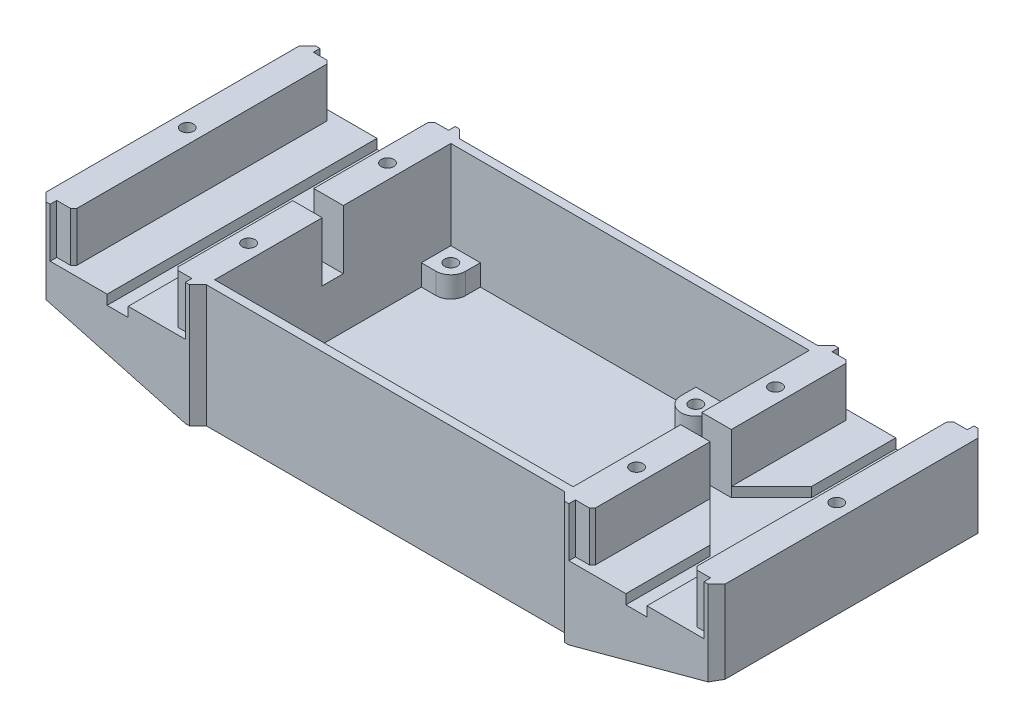
SolidWorks part; units mm, degrees
material "Nylon 101"
ref_plane "Front Plane" through (0, 0, 0) normal (0, 0, 1) x (1, 0, 0)
ref_plane "Top Plane" through (0, 0, 0) normal (0, 1, 0) x (1, 0, 0)
ref_plane "Right Plane" through (0, 0, 0) normal (1, 0, 0) x (0, 0, -1)
sketch "Sketch1" plane through (0, 0, 0) normal (0, 1, 0) x (1, 0, 0)
  line L0 (-42.5, 0) -> (42.5, 0) construction
  line L1 (-42.5, -28) -> (42.5, -28)
  line L2 (-42.5, -28) -> (-42.5, 28)
  line L3 (-42.5, 28) -> (42.5, 28)
  line L4 (42.5, -28) -> (42.5, 28)
  line L5 (-42.5, -28) -> (42.5, 28) construction
  line L6 (-42.5, 28) -> (42.5, -28) construction
  line L11 (-39, 0) -> (-39, -24.5) construction
  line L12 (-39, 0) -> (-39, 24.5) construction
  line L13 (19.09, 0) -> (19.09, 24.5) construction
  line L14 (19.09, 0) -> (19.09, -24.5) construction
  line L16 (-44.5, -30) -> (44.5, -30)
  line L17 (-44.5, -30) -> (-44.5, 30)
  line L18 (-44.5, 30) -> (44.5, 30)
  line L19 (44.5, -30) -> (44.5, 30)
  circle A0 centre (-39, 24.5) radius 1.5
  circle A1 centre (19.09, 24.5) radius 1.5
  circle A2 centre (-39, -24.5) radius 1.5
  circle A3 centre (19.09, -24.5) radius 1.5
  circle A4 centre (-39, 24.5) radius 3.5
  circle A5 centre (19.09, 24.5) radius 3.5
  circle A6 centre (-39, -24.5) radius 3.5
  circle A7 centre (19.09, -24.5) radius 3.5
  point P0 (0, 0)
  point P6 (0, 0)
  dimension "D9" = 3
  dimension "D10" = 3
  dimension "D11" = 3
  dimension "D12" = 3
  dimension "D13" = 7
  dimension "D14" = 7
  dimension "D15" = 7
  dimension "D16" = 7
  dimension "D1" = 85
  dimension "D2" = 56
  dimension "D3" = 39
  dimension "D4" = 24.5
  dimension "D5" = 24.5
  dimension "D6" = 19.09
  dimension "D7" = 24.5
  dimension "D8" = 24.5
  dimension "D17" = 2
  dimension "D18" = 2
  dimension "D19" = 2
  dimension "D20" = 2
sketch "Sketch2" plane through (0, 0, 0) normal (0, 1, 0) x (1, 0, 0)
  line L1 (-42.5, -28) -> (42.5, -28)
  line L2 (-42.5, -28) -> (-42.5, 28)
  line L3 (-42.5, 28) -> (42.5, 28)
  line L4 (42.5, -28) -> (42.5, 28)
extrude "Boss-Extrude4" add sketch "Sketch2" along normal blind 3
sketch "Sketch3" plane through (0, 0, 0) normal (0, 1, 0) x (1, 0, 0)
  line L0 (0, 0) -> (-44.5, 0) construction
  line L1 (-44.5, -30) -> (44.5, -30)
  line L2 (-44.5, -30) -> (-44.5, 30)
  line L3 (-44.5, 30) -> (44.5, 30)
  line L4 (44.5, -30) -> (44.5, 30)
  line L5 (-42.5, 28) -> (42.5, 28)
  line L6 (-42.5, 28) -> (-42.5, -28)
  line L7 (-42.5, -28) -> (42.5, -28)
  line L8 (42.5, 28) -> (42.5, -28)
  line L9 (-44.5, 0) -> (-78.5, 0) construction
  line L10 (-44.5, 30) -> (-44.5, 32)
  line L11 (-44.5, 32) -> (-78.5, 32)
  line L12 (-78.5, 32) -> (-78.5, 0)
  line L13 (-78.5, 0) -> (-78.5, -32)
  line L14 (-78.5, -32) -> (-44.5, -32)
  line L15 (-44.5, -32) -> (-44.5, -30)
  line L16 (0, 0) -> (44.5, 0) construction
  line L17 (44.5, 0) -> (78.5, 0) construction
  line L18 (44.5, 30) -> (44.5, 32)
  line L19 (44.5, 32) -> (78.5, 32)
  line L20 (78.5, 32) -> (78.5, 0)
  line L21 (78.5, 0) -> (78.5, -32)
  line L22 (78.5, -32) -> (44.5, -32)
  line L23 (44.5, -32) -> (44.5, -30)
  dimension "D1" = 44.5
  dimension "D2" = 34
  dimension "D3" = 2
  dimension "D4" = 2
  dimension "D5" = 34
  dimension "D6" = 2
  dimension "D7" = 2
extrude "Boss-Extrude5" add sketch "Sketch3" along normal blind 29 contours L1 L4 L3 L2 L5 L8 L7 L6 | L14 L15 L2 L10 L11 L12 L13 | L23 L22 L21 L20 L19 L18 L4 region at (-43.4266, 0, 0) region at (-61.5, 0, 0) region at (61.5, 0, 0)
sketch "Sketch5" plane through (0, 0, 0) normal (0, 1, 0) x (1, 0, 0)
  line L0 (15.59, 24.5) -> (15.59, 28)
  line L1 (-42.5, -28) -> (42.5, -28)
  line L2 (-42.5, -28) -> (-42.5, 28)
  line L3 (-42.5, 28) -> (42.5, 28)
  line L4 (42.5, -28) -> (42.5, 28)
  line L5 (22.59, 24.5) -> (22.59, 28)
  line L6 (15.59, -24.5) -> (15.59, -28)
  line L7 (22.59, -24.5) -> (22.59, -28)
  line L8 (-39, -21) -> (-42.5, -21)
  line L9 (-35.5, -24.5) -> (-35.5, -28)
  line L10 (-39, 21) -> (-42.5, 21)
  line L11 (-35.5, 24.5) -> (-35.5, 28)
  circle A0 centre (19.09, 24.5) radius 3.5
  circle A1 centre (19.09, -24.5) radius 3.5
  circle A2 centre (-39, 24.5) radius 3.5
  circle A3 centre (-39, -24.5) radius 3.5
extrude "Boss-Extrude10" add sketch "Sketch5" along normal blind 8 contours A2 | A2 L3 L2 | A2 L2 L10 | A2 L11 L3 | A3 L1 L9 | A3 | A3 L2 L1 | A3 L8 L2 | A1 L1 L7 | A1 | A1 L6 L1 | A0 L5 L3 | A0 L3 L0 | A0 region at (19.09, 0, -24.5) region at (16.3718, 0, -27.2182) region at (21.8082, 0, -27.2182) region at (-36.2818, 0, -27.2182) region at (-41.7182, 0, -27.2182) region at (-39, 0, -24.5) region at (-41.7182, 0, -21.7818) region at (21.8082, 0, 27.2182) region at (-41.7182, 0, 21.7818) region at (16.3718, 0, 27.2182) region at (19.09, 0, 24.5) region at (-41.7182, 0, 27.2182) region at (-39, 0, 24.5) region at (-36.2818, 0, 27.2182)
sketch "Sketch6" plane through (0, 29, 0) normal (0, 1, 0) x (1, 0, 0)
  line L0 (-44.5, 30) -> (-44.5, -30) construction
  line L1 (-44.5, -32) -> (-45.475, -32)
  line L2 (-78.5, -32) -> (-44.5, -32) construction
  line L3 (44.5, 30) -> (44.5, -30) construction
  line L4 (-45.475, -32) -> (-77.525, -32)
  line L5 (-77.525, -32) -> (-78.5, -32)
  line L6 (-44.5, 32) -> (-45.48, 32)
  line L7 (-44.5, 32) -> (-78.5, 32) construction
  line L8 (-45.48, 32) -> (-77.53, 32)
  line L9 (-77.53, 32) -> (-78.5, 32)
  line L10 (-61.5, -32) -> (-61.505, 32) construction
  line L11 (-77.525, -32) -> (-77.525, -30.43)
  line L12 (-77.525, -30.43) -> (-45.475, -30.43)
  line L13 (-45.475, -30.43) -> (-45.475, -32)
  line L14 (-77.53, 32) -> (-77.53, 30.43)
  line L15 (-77.53, 30.43) -> (-45.48, 30.43)
  line L16 (-45.48, 30.43) -> (-45.48, 32)
  line L17 (-61.5025, 0) -> (-73.5025, 0) construction
  line L18 (-61.5025, 0) -> (-49.5025, 0) construction
  line L19 (-73.5025, 0) -> (-73.5025, -30.43)
  line L20 (-73.5025, 0) -> (-73.5025, 30.43)
  line L21 (-49.5025, 0) -> (-49.5025, 30.43)
  line L22 (-49.5025, 0) -> (-49.5025, -30.43)
  line M21 (-44.5, 32) -> (-78.5, 32)
  line M23 (-78.5, -32) -> (-44.5, -32)
  dimension "D1" = 34
  dimension "D2" = 32.05
  dimension "D3" = 0.975
  dimension "D4" = 0.975
  dimension "D5" = 0.98
  dimension "D6" = 32.05
  dimension "D7" = 0.97
  dimension "D8" = 1.57
  dimension "D9" = 1.57
  dimension "D10" = 1.57
  dimension "D11" = 1.57
  dimension "D12" = 12
  dimension "D13" = 12
extrude "Cut-Extrude1" cut sketch "Sketch6" against normal blind 11.7 contours L15 L16 L14 M21 | L22 L21 L15 L20 L19 L12 | L13 L12 L11 M23 region at (-61.5, 29, 31.215) region at (-61.5025, 29, 0) region at (-61.505, 29, -31.215)
chamfer "Chamfer1" distance 2 angle 45 4 edges at (-44.5, 14.5, -30) (44.5, 14.5, -30) (44.5, 14.5, 30) (-44.5, 14.5, 30)
sketch "Sketch7" plane through (0, 29, 0) normal (0, 1, 0) x (1, 0, 0)
  line L0 (61.5, 32) -> (61.5, -32) construction
  line L1 (44.5, 32) -> (78.5, 32) construction
  line L2 (78.5, -32) -> (44.5, -32) construction
  line L3 (61.5, 32) -> (45.475, 32)
  line L4 (61.5, 32) -> (77.53, 32)
  line L5 (77.53, 32) -> (77.53, 30.43)
  line L6 (77.53, 30.43) -> (73.5, 30.43)
  line L7 (73.5, 30.43) -> (73.5, -30.43)
  line L8 (73.5, -30.43) -> (77.53, -30.43)
  line L9 (77.53, -30.43) -> (77.53, -32)
  line L10 (77.53, -32) -> (61.5, -32)
  line L11 (61.5, -32) -> (45.47, -32)
  line L12 (45.47, -32) -> (45.47, -30.43)
  line L13 (45.47, -30.43) -> (49.5, -30.43)
  line L14 (49.5, -30.43) -> (49.5, 30.43)
  line L15 (49.5, 30.43) -> (45.475, 30.43)
  line L16 (45.475, 30.43) -> (45.475, 32)
  dimension "D1" = 16.025
  dimension "D2" = 16.03
  dimension "D3" = 1.57
  dimension "D4" = 1.57
  dimension "D5" = 12
  dimension "D6" = 12
  dimension "D7" = 1.57
  dimension "D8" = 16.03
  dimension "D9" = 16.03
  dimension "D10" = 1.57
extrude "Cut-Extrude2" cut sketch "Sketch7" against normal blind 11.7
sketch "Sketch8" plane through (-78.5, 0, 0) normal (-1, 0, 0) x (0, 0, 1)
  line L1 (-32, 29) -> (32, 29)
  line L2 (-32, 29) -> (-32, 0)
  line L3 (-32, 0) -> (32, 0)
  line L4 (32, 29) -> (32, 0)
extrude "Boss-Extrude11" add sketch "Sketch8" along normal blind 2
sketch "Sketch9" plane through (78.5, 0, 0) normal (1, 0, 0) x (0, 0, -1)
  line L1 (-32, 29) -> (32, 29)
  line L2 (-32, 29) -> (-32, 0)
  line L3 (-32, 0) -> (32, 0)
  line L4 (32, 29) -> (32, 0)
extrude "Boss-Extrude12" add sketch "Sketch9" along normal blind 2
chamfer "Chamfer2" distance 2 angle 45 4 edges at (-80.5, 14.5, -32) (80.5, 14.5, -32) (80.5, 14.5, 32) (-80.5, 14.5, 32)
chamfer "Chamfer3" distance 0.75 angle 45 8 edges at (-73.5025, 23.15, -30.43) (-49.5025, 23.15, -30.43) (-73.5025, 23.15, 30.43) (-49.5025, 23.15, 30.43) (73.5, 23.15, 30.43) (49.5, 23.15, 30.43) (49.5, 23.15, -30.43) (73.5, 23.15, -30.43)
sketch "Sketch10" plane through (0, 29, 0) normal (0, 1, 0) x (1, 0, 0)
  line L0 (-61.505, 32) -> (-61.5, -32) construction
  line L1 (-45.48, 32) -> (-77.53, 32) construction
  line L2 (-77.525, -32) -> (-45.475, -32) construction
  line L3 (61.5025, 32) -> (61.5, -32) construction
  line L4 (77.53, 32) -> (45.475, 32) construction
  line L5 (45.47, -32) -> (77.53, -32) construction
  line L6 (-61.505, 32) -> (-64.005, 32)
  line L7 (-64.005, 32) -> (-64.005, -32)
  line L8 (-64.005, -32) -> (-61.5, -32)
  line L9 (-61.5, -32) -> (-59.005, -32)
  line L10 (-59.005, -32) -> (-59.005, 32)
  line L11 (-59.005, 32) -> (-61.505, 32)
  line L12 (61.5025, 32) -> (59.0025, 32)
  line L13 (59.0025, 32) -> (59.0025, -32)
  line L14 (59.0025, -32) -> (61.5, -32)
  line L15 (61.5, -32) -> (64.0025, -32)
  line L16 (64.0025, -32) -> (64.0025, 32)
  line L17 (64.0025, 32) -> (61.5025, 32)
  line L18 (-59.005, 0) -> (59.0025, 0) construction
  line L19 (-59.005, 0) -> (-59.005, 2.5)
  line L20 (-59.005, 2.5) -> (59.0025, 2.5)
  line L21 (59.0025, 2.5) -> (59.0025, 0)
  line L22 (59.0025, 0) -> (59.0025, -2.5)
  line L23 (59.0025, -2.5) -> (-59.005, -2.5)
  line L24 (-59.005, -2.5) -> (-59.005, 0)
  line M3 (-49.5025, 29.68) -> (-49.5025, -29.68)
  line M15 (49.5, -29.68) -> (49.5, 29.68)
  line M26 (42.5, 28) -> (42.5, -28)
  line M28 (-42.5, -28) -> (-42.5, 28)
  dimension "D1" = 2.5
  dimension "D2" = 2.5
  dimension "D3" = 2.5
  dimension "D4" = 2.5
  dimension "D5" = 2.5
  dimension "D6" = 2.5
sketch "Sketch11" plane through (0, 0, 32) normal (0, 0, 1) x (1, 0, 0)
  line L0 (-77.525, 17.3) -> (-77.525, 0) construction
  line L1 (-78.5, 0) -> (-44.5, 0) construction
  line L2 (-45.475, 17.3) -> (-45.475, 0) construction
  line L3 (-77.525, 8.65) -> (-45.475, 0)
  line L4 (-45.475, 0) -> (-93.8507, 13.0561)
  line L5 (45.47, 17.3) -> (45.47, 0) construction
  line L6 (78.5, 0) -> (44.5, 0) construction
  line L7 (77.53, 17.3) -> (77.53, 0) construction
  line L8 (45.47, 0) -> (77.53, 8.65)
  line L9 (77.53, 8.65) -> (97.2513, 13.971)
  line L10 (97.2513, 13.971) -> (104.6271, -13.3661)
  line L11 (104.6271, -13.3661) -> (45.47, 0)
  line L12 (-93.8507, 13.0561) -> (-80.7472, -16.8754)
  line L13 (-80.7472, -16.8754) -> (-45.475, 0)
  line M5 (-78.5, 29) -> (-78.5, 0)
  line M6 (-78.5, 0) -> (-44.5, 0)
extrude "Cut-Extrude4" cut sketch "Sketch11" against normal through all contours L11 L10 L9 L8 | L12 L13 L4 M6 M5 | L3 L4 M5 M6 region at (-67.4917, 2.971, 32) region at (-75.115, -2.5446, 32) region at (82.4495, 0.2016, 32)
extrude "Cut-Extrude5" cut sketch "Sketch10" against normal blind 14 contours L10 L11 L6 L7 L8 L9 | L23 L20 L10 M3 | L23 L20 M28 M3 | L23 L20 M26 M28 | L23 L20 M15 M26 | L23 L13 L20 M15 | L16 L17 L12 L13 L14 L15 region at (-61.505, 29, 0) region at (-54.2538, 29, 0) region at (-46.0013, 29, 0) region at (0, 29, 0) region at (46, 29, 0) region at (54.2512, 29, 0) region at (61.5025, 29, 0)
chamfer "Chamfer4" distance 9.5 angle 45 4 edges at (59.0025, 16.15, -2.5) (59.0025, 16.15, 2.5) (-59.005, 16.15, 2.5) (-59.005, 16.15, -2.5)
sketch "Sketch14" plane through (0, 8, 0) normal (0, 1, 0) x (1, 0, 0)
  circle A0 centre (19.09, -24.5) radius 3.5
  circle A1 centre (19.09, -24.5) radius 1.5
  circle A2 centre (-39, -24.5) radius 3.5
  circle A3 centre (-39, -24.5) radius 1.5
  circle A4 centre (-39, 24.5) radius 3.5
  circle A5 centre (-39, 24.5) radius 1.5
  circle A6 centre (19.09, 24.5) radius 3.5
  circle A7 centre (19.09, 24.5) radius 1.5
  dimension "D1" = 3
  dimension "D2" = 3
  dimension "D3" = 3
  dimension "D4" = 3
extrude "Cut-Extrude7" cut sketch "Sketch14" against normal blind 5 contours A5 | A7 | A1 | A3
sketch "Sketch15" plane through (0, 29, 0) normal (0, 1, 0) x (1, 0, 0)
  line L0 (-46.0025, 2.5) -> (-46.0025, 30.43) construction
  line L1 (-49.505, 2.5) -> (-42.5, 2.5) construction
  line L2 (-48.7525, 30.43) -> (-45.48, 30.43) construction
  line L3 (-46.0013, -2.5) -> (-46.0013, -30.43) construction
  line L4 (-42.5, -2.5) -> (-49.5025, -2.5) construction
  line L5 (-48.7525, -30.43) -> (-45.475, -30.43) construction
  line L6 (-73.5025, 0) -> (-80.5, 0) construction
  line L7 (-73.5025, -29.68) -> (-73.5025, 29.68) construction
  line L8 (-80.5, -30) -> (-80.5, 30) construction
  line L9 (73.5, 0) -> (80.5, 0) construction
  line L10 (73.5, -29.68) -> (73.5, 29.68) construction
  line L11 (80.5, 30) -> (80.5, -30) construction
  line L12 (46, 2.5) -> (46, 30.43) construction
  line L13 (42.5, 2.5) -> (49.5, 2.5) construction
  line L14 (45.475, 30.43) -> (48.75, 30.43) construction
  line L15 (46, -2.5) -> (46, -30.43) construction
  line L16 (49.5, -2.5) -> (42.5, -2.5) construction
  line L17 (48.75, -30.43) -> (45.47, -30.43) construction
  circle A0 centre (46, 16.465) radius 1.5
  circle A1 centre (46, -16.465) radius 1.5
  circle A2 centre (77, 0) radius 1.5
  circle A3 centre (-46.0025, 16.465) radius 1.5
  circle A4 centre (-46.0013, -16.465) radius 1.5
  circle A5 centre (-77.0013, 0) radius 1.5
  dimension "D1" = 3
  dimension "D2" = 3
  dimension "D3" = 3
  dimension "D4" = 3
  dimension "D5" = 3
  dimension "D6" = 3
extrude "Cut-Extrude8" cut sketch "Sketch15" against normal blind 5
